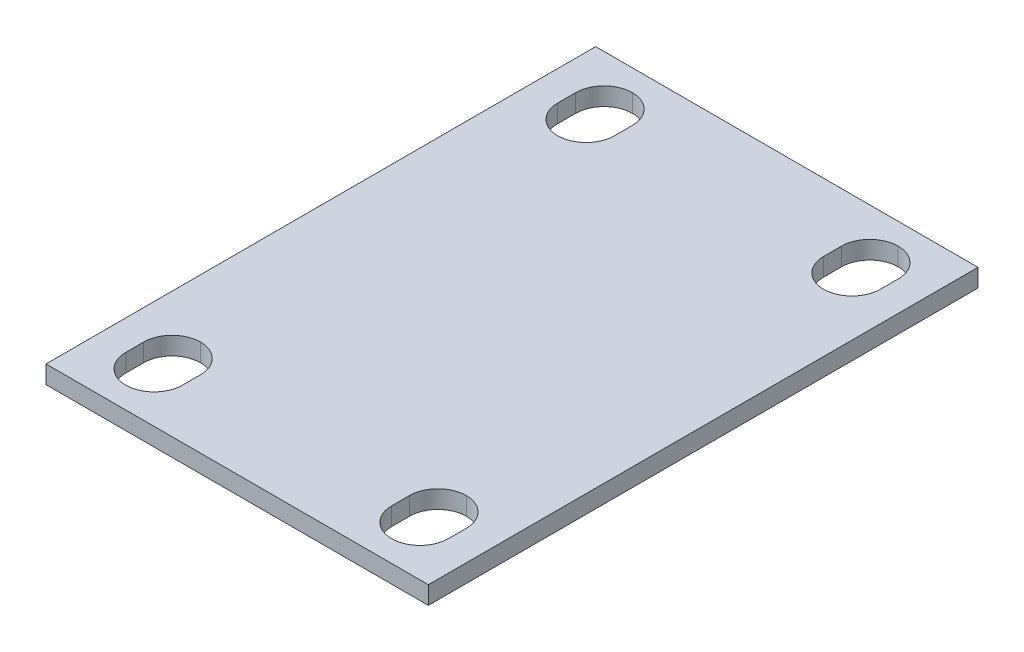
SolidWorks part; units mm, degrees
ref_plane "Front Plane" through (0, 0, 0) normal (0, 0, 1) x (1, 0, 0)
ref_plane "Top Plane" through (0, 0, 0) normal (0, 1, 0) x (1, 0, 0)
ref_plane "Right Plane" through (0, 0, 0) normal (1, 0, 0) x (0, 0, -1)
sketch "Sketch1" plane through (0, 0, 0) normal (0, 1, 0) x (1, 0, 0)
  line L1 (32, 46) -> (-32, 46)
  line L2 (32, 46) -> (32, -46)
  line L3 (32, -46) -> (-32, -46)
  line L4 (-32, 46) -> (-32, -46)
  dimension "D1" = 92
  dimension "D2" = 64
  dimension "D3" = 32
  dimension "D4" = 46
extrude "Boss-Extrude1" add sketch "Sketch1" along normal blind 3
sketch "Sketch2" plane through (0, 3, 0) normal (0, 1, 0) x (1, 0, 0)
  line L0 (27, 46) -> (27, -46) construction
  line L1 (32, 46) -> (-32, 46) construction
  line L2 (-32, -46) -> (32, -46) construction
  line L3 (32, -46) -> (32, 46) construction
  line L4 (32.8285, 42.4) -> (-42.3475, 42.4) construction
  line L5 (0, 48.9376) -> (0, -49.5478) construction
  line L6 (50.8284, 0) -> (-57.2612, 0) construction
  line L7 (27, 29.9) -> (17.5, 29.9)
  line L8 (27, 29.9) -> (27, 42.4)
  line L9 (27, 42.4) -> (17.5, 42.4)
  line L10 (17.5, 29.9) -> (17.5, 42.4)
  line L11 (-27, 42.4) -> (-17.5, 42.4)
  line L12 (-17.5, 29.9) -> (-17.5, 42.4)
  line L13 (-27, 29.9) -> (-17.5, 29.9)
  line L14 (-27, 29.9) -> (-27, 42.4)
  line L15 (27, -42.4) -> (17.5, -42.4)
  line L16 (17.5, -29.9) -> (17.5, -42.4)
  line L17 (27, -29.9) -> (17.5, -29.9)
  line L18 (27, -29.9) -> (27, -42.4)
  line L19 (-27, -29.9) -> (-27, -42.4)
  line L20 (-27, -29.9) -> (-17.5, -29.9)
  line L21 (-17.5, -29.9) -> (-17.5, -42.4)
  line L22 (-27, -42.4) -> (-17.5, -42.4)
  dimension "D1" = 5
  dimension "D2" = 3.6
  dimension "D3" = 9.5
  dimension "D4" = 12.5
extrude "Cut-Extrude1" cut sketch "Sketch2" against normal up to surface (3 mm away) up to face at (0, 0, 0)
fillet "Fillet1" radius 4.75 16 edges at (27, 1.5, 42.4) (17.5, 1.5, 42.4) (17.5, 1.5, 29.9) (27, 1.5, 29.9) (-27, 1.5, 42.4) (-17.5, 1.5, 42.4) (-17.5, 1.5, 29.9) (-27, 1.5, 29.9) (27, 1.5, -29.9) (17.5, 1.5, -29.9) (27, 1.5, -42.4) (17.5, 1.5, -42.4) (-17.5, 1.5, -29.9) (-27, 1.5, -29.9) (-17.5, 1.5, -42.4) (-27, 1.5, -42.4)
sketch "Sketch5" plane through (0, 0, 0) normal (1, 0, 0) x (0, 0, -1)
  line L0 (0, -11.8428) -> (0, 22.7187) construction
  line L1 (13, 22.7187) -> (13, -11.8428) construction
  line L2 (17, 22.7187) -> (17, -11.8428) construction
  line L3 (-45.8034, 6) -> (46.635, 6) construction
  line L4 (-46, 3) -> (46, 3) construction
  line L5 (17, 3) -> (13, 6)
  line L6 (17, 3) -> (13, 3) construction
  line L7 (17, 3) -> (17, 6) construction
  line L8 (17, 6) -> (13, 6) construction
  line L9 (13, 3) -> (13, 6) construction
  line L10 (9, 22.7187) -> (9, -11.8428) construction
  line L11 (-27.52, 8.5) -> (47.928, 8.5) construction
  line L12 (-27.52, 13) -> (47.928, 13) construction
  line L13 (7, 22.7187) -> (7, -11.8428) construction
  line L14 (13, 6) -> (9, 6) construction
  line L15 (13, 6) -> (13, 8.5) construction
  line L16 (13, 8.5) -> (9, 8.5) construction
  line L17 (9, 6) -> (9, 8.5) construction
  line L19 (9, 8.5) -> (7, 8.5) construction
  line L20 (9, 8.5) -> (9, 13) construction
  line L21 (9, 13) -> (7, 13) construction
  line L22 (7, 8.5) -> (7, 13) construction
  line L24 (7, 13) -> (0, 13)
  line L25 (0, 13) -> (0, 3)
  line L26 (0, 3) -> (17, 3)
  point P33 (11.8737, 6.8251)
  point P34 (10.1369, 7.6534)
  point P36 (9, 7.2487)
  dimension "D1" = 13
  dimension "D2" = 17
  dimension "D3" = 3
  dimension "D4" = 0
  dimension "D5" = 9
  dimension "D6" = 2.5
  dimension "D7" = 10
  dimension "D8" = 7
